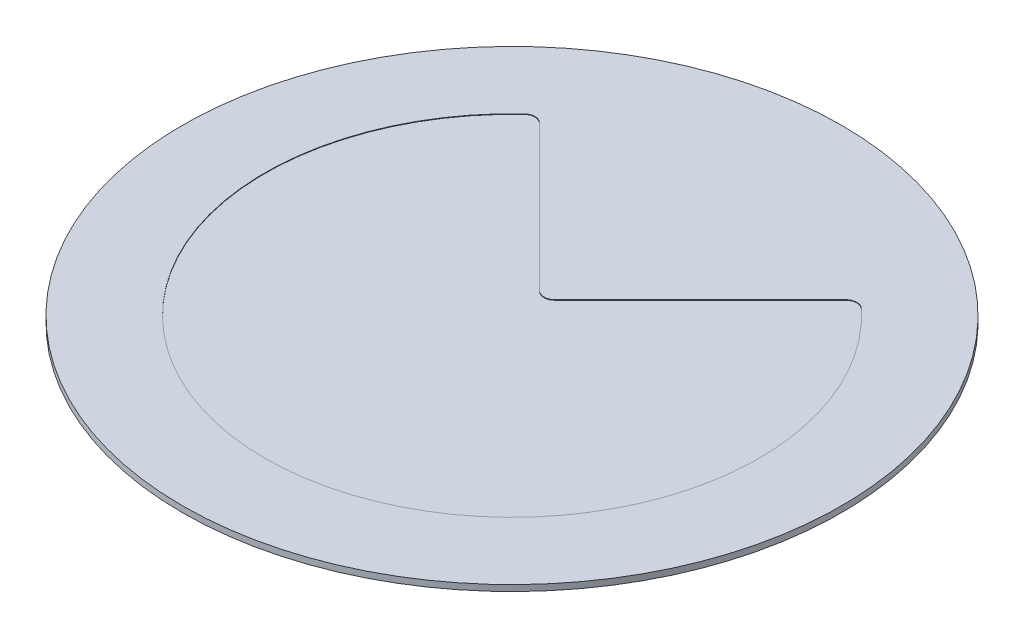
SolidWorks part; units mm, degrees
ref_plane "Front" through (0, 0, 0) normal (0, 0, 1) x (1, 0, 0)
ref_plane "Top" through (0, 0, 0) normal (0, 1, 0) x (1, 0, 0)
ref_plane "Right" through (0, 0, 0) normal (1, 0, 0) x (0, 0, -1)
sketch "Sketch1" plane through (0, 0, 0) normal (0, 1, 0) x (1, 0, 0)
  line L1 (0, 55.799) -> (0, -45) construction
  line L3 (-29.2214, 34.2214) -> (0, 5)
  line L4 (0, 5) -> (29.2214, 34.2214)
  line L5 (0, -50) -> (0, -56.3751) construction
  arc A2 (-29.2214, 34.2214) -> (29.2214, 34.2214) centre (0, 0) ccw
  circle A3 centre (0, 0) radius 60
  dimension "D1" = 120
  dimension "D3" = 90
  dimension "D4" = 90
  dimension "D5" = 5
extrude "Boss-Extrude1" add sketch "Sketch1" along normal blind 0.1
fillet "Fillet1" radius 2 3 edges at (-29.2214, 0.05, -34.2214) (29.2214, 0.05, -34.2214) (0, 0.05, -5)
sketch "Sketch2" plane through (0, 0, 0) normal (0, -1, 0) x (1, 0, 0)
  circle A0 centre (0, 0) radius 60
extrude "Boss-Extrude2" add sketch "Sketch2" along normal blind 1
